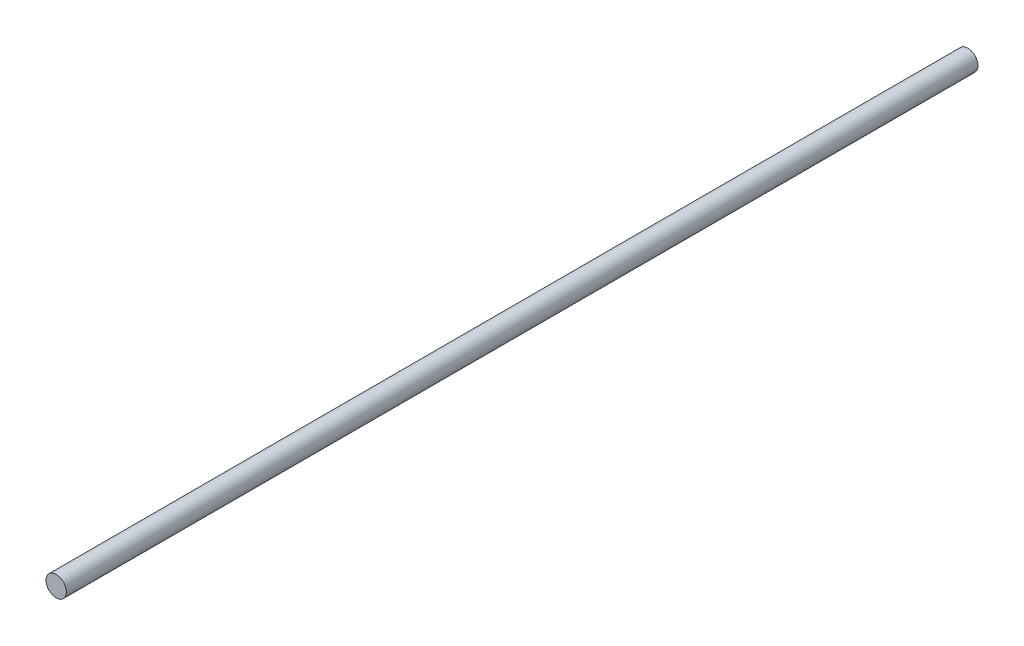
SolidWorks part; units mm, degrees
ref_plane "Front Plane" through (0, 0, 0) normal (0, 0, 1) x (1, 0, 0)
ref_plane "Top Plane" through (0, 0, 0) normal (0, 1, 0) x (1, 0, 0)
ref_plane "Right Plane" through (0, 0, 0) normal (1, 0, 0) x (0, 0, -1)
sketch "Sketch1" plane through (0, 0, 0) normal (0, 0, 1) x (1, 0, 0)
  circle A0 centre (10.0166, -10.0166) radius 3.7971
  dimension "D1" = 7.5942
extrude "Boss-Extrude1" add sketch "Sketch1" against normal blind 300
extrude "Boss-Extrude2" add sketch "Sketch1<2>" along normal blind 40
sketch "Sketch1<2>" plane through (0, 0, 0) normal (0, 0, 1) x (1, 0, 0) same geometry as "Sketch1"
